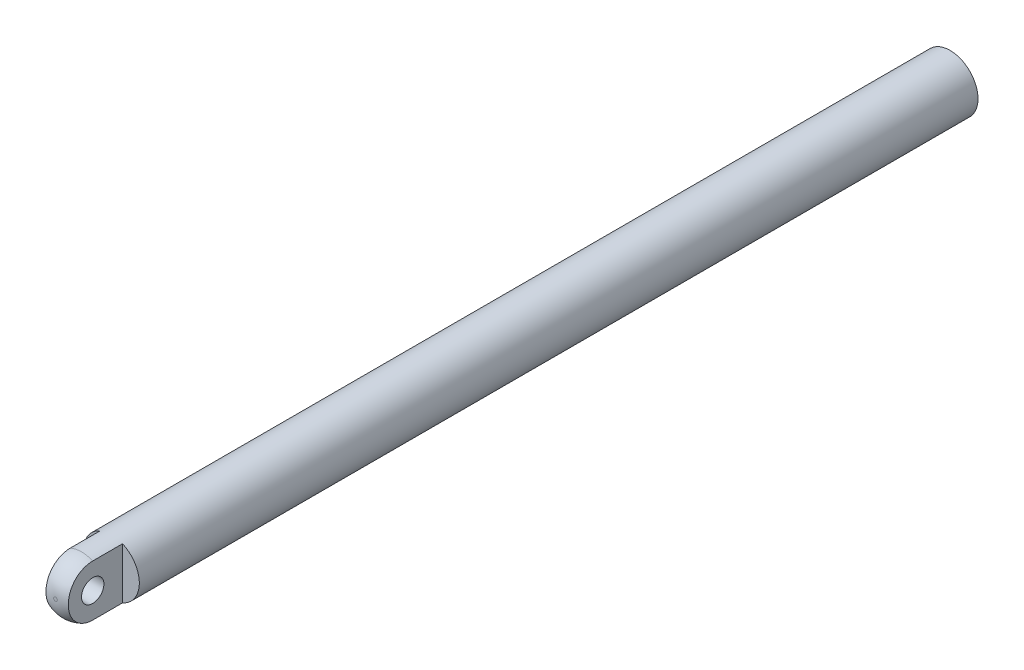
SolidWorks part; units mm, degrees
ref_plane "前视基准面" through (0, 0, 0) normal (0, 0, 1) x (1, 0, 0)
ref_plane "上视基准面" through (0, 0, 0) normal (0, 1, 0) x (1, 0, 0)
ref_plane "右视基准面" through (0, 0, 0) normal (1, 0, 0) x (0, 0, -1)
sketch "草图1" plane through (0, 0, 0) normal (0, 0, 1) x (1, 0, 0)
  circle A0 centre (0, 0) radius 75
  dimension "D1" = 150
extrude "凸台-拉伸1" add sketch "草图1" along normal blind 2400
sketch "草图2" plane through (0, 0, 2400) normal (0, 0, 1) x (1, 0, 0)
  line L1 (-30, 75) -> (-30, -75)
  line L2 (30, 75) -> (30, -75)
  line L3 (30, 75) -> (106.4586, 55.8296)
  line L4 (106.4586, 55.8296) -> (106.4586, -47.8758)
  line L5 (106.4586, -47.8758) -> (30, -75)
  line L6 (-30, -75) -> (-133.0733, -42.3693)
  line L7 (-133.0733, -42.3693) -> (-77.3966, 65.4148)
  line L8 (-77.3966, 65.4148) -> (-30, 75)
extrude "切除-拉伸1" cut sketch "草图2" against normal blind 150
sketch "草图3" plane through (30, 0, 0) normal (1, 0, 0) x (0, 0, -1)
  line L0 (-2250, 68.7386) -> (-2250, -68.7386) construction
  circle A0 centre (-2330, 0) radius 30
  point P2 (-2250, 0)
  dimension "D1" = 80
extrude "切除-拉伸2" cut sketch "草图3" against normal blind 150
fillet "圆角1" radius 70 1 edges at (0, 75, 2400)
sketch "草图4" plane through (0, 0, 0) normal (0, 0, -1) x (-1, 0, 0)
  circle A0 centre (0, 0) radius 60
extrude "切除-拉伸4" cut sketch "草图4" against normal blind 2200
scale "缩放比例1" scale about origin uniform scaling yes scale factor 0.345
